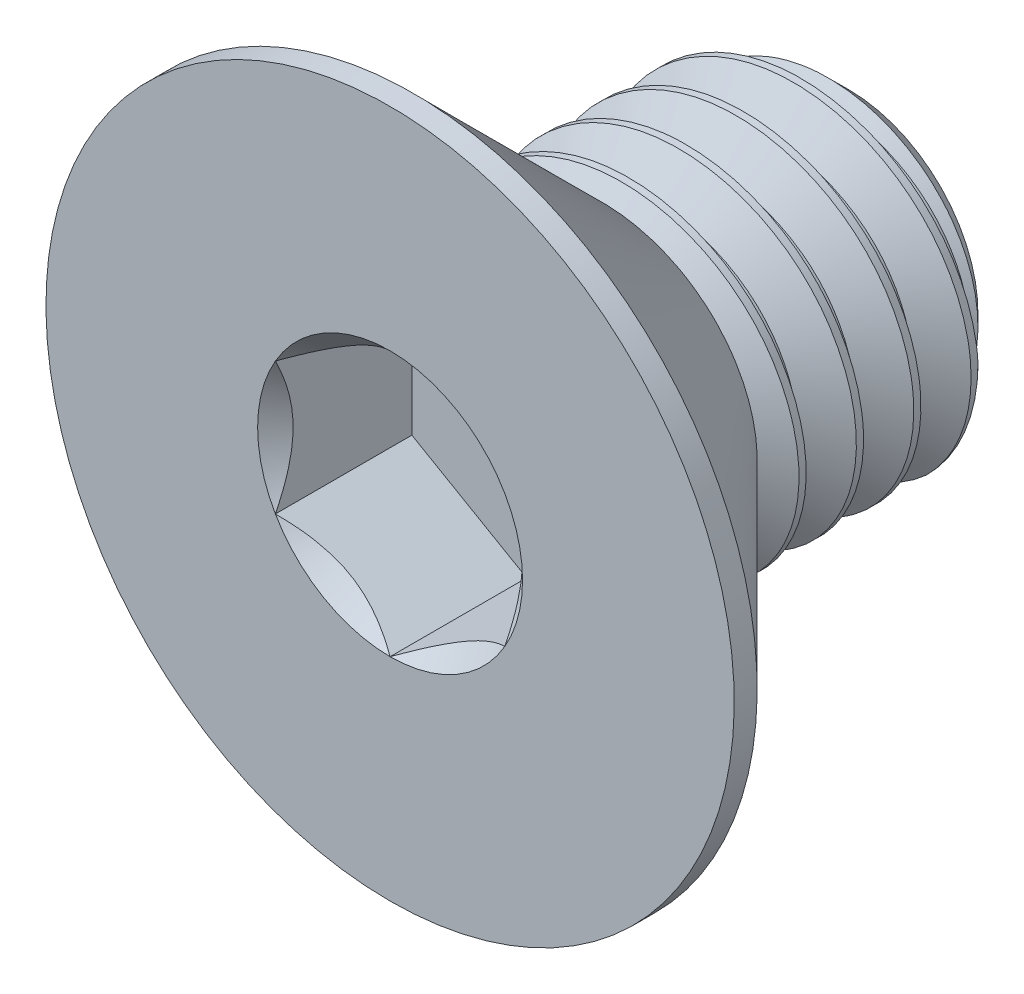
SolidWorks part; units mm, degrees
ref_plane "Front" through (0, 0, 0) normal (0, 0, 1) x (1, 0, 0)
ref_plane "Top" through (0, 0, 0) normal (0, 1, 0) x (1, 0, 0)
ref_plane "Right" through (0, 0, 0) normal (1, 0, 0) x (0, 0, -1)
sketch "Sketch1" plane through (0, 0, 0) normal (1, 0, 0) x (0, 0, -1)
  line L0 (0, 3) -> (0.2, 3) construction
  line L1 (0.2, 3) -> (1.7, 1.5) construction
  line L2 (0, 1.5) -> (4, 1.5)
  line L3 (4, 1.5) -> (4, 0)
  line L4 (4, 0) -> (0, 0)
  line L5 (0, 0) -> (0, 3) construction
  line L6 (0, 3) -> (0, -3) construction
  line L7 (4, 1.5) -> (4, -1.5) construction
  line L8 (0, -3) -> (0.2, -3) construction
  line L9 (0.2, -3) -> (1.7, -1.5) construction
  line L11 (0, 1.5) -> (0, 0)
  line L12 (1.7, 1.5) -> (1.7, 0) construction
revolve "Revolve1" add sketch "Sketch1" angle 360 mid plane about L4
sketch "Sketch3" plane through (0, 0, -4) normal (0, 0, -1) x (-1, 0, 0)
  circle A0 centre (0, 0) radius 1.5
curve "Helix/Spiral1" pitch 0.5 height 4 radius 1.5 centre (0, 0, -4) axis (0, 0, 1) start towards (0, 1, 0)
sketch "Sketch2" plane through (0, 0, 0) normal (1, 0, 0) x (0, 0, -1)
  line L0 (4, 1.5) -> (4.4375, 1.5)
  line L1 (4.4375, 1.5) -> (4.25, 1.1752)
  line L2 (4.25, 1.1752) -> (4.1875, 1.1752)
  line L3 (4.1875, 1.1752) -> (4, 1.5)
  line L4 (4.0938, 1.3376) -> (4.3437, 1.3376) construction
  dimension "D1" = 60
  dimension "D2" = 0.0625
  dimension "D3" = 0.25
chamfer "Chamfer1" distance 0.375 angle 45 1 edges at (0, 1.5, -4)
sweep "Cut-Sweep1" cut profiles "Sketch2" path "Helix/Spiral1" align with end faces yes
sketch "Sketch7" plane through (0, 0, 0) normal (1, 0, 0) x (0, 0, -1)
  line L0 (0, 3) -> (0.2, 3) construction
  line L1 (0.2, 3) -> (1.7, 1.5) construction
  line L2 (0, 3) -> (0.2, 3)
  line L3 (0.2, 3) -> (1.7, 1.5)
  line L4 (1.7, 1.5) -> (1.7, 0) construction
  line L5 (1.7, 1.5) -> (1.7, 0)
  line L7 (0, 0) -> (0, 3) construction
  line L8 (0, 0) -> (0, 3)
  line L9 (0, 0) -> (1.7, 0)
  line L10 (3.3, 0) -> (-3.3, 0) construction
revolve "Revolve2" add sketch "Sketch7" angle 360 mid plane about L9
ref_plane "Plane1" through (0, 0, -1.7) normal (0, 0, 1) x (1, 0, 0)
sketch "Sketch8" plane through (0, 0, -1.7) normal (0, 0, 1) x (1, 0, 0)
  circle A0 centre (0, 0) radius 1.5
extrude "Boss-Extrude1" add sketch "Sketch8" against normal through all draft 45
sketch "Sketch5" plane through (0, 0, 0) normal (0, 0, 1) x (1, 0, 0)
  line L1 (1, -0.5774) -> (1, 0.5774)
  line L2 (1, 0.5774) -> (0, 1.1547)
  line L3 (0, 1.1547) -> (-1, 0.5774)
  line L4 (-1, 0.5774) -> (-1, -0.5774)
  line L5 (-1, -0.5774) -> (0, -1.1547)
  line L6 (0, -1.1547) -> (1, -0.5774)
  circle A0 centre (0, 0) radius 1 construction
  dimension "Hex" = 2
extrude "Cut-Extrude2" cut sketch "Sketch5" against normal blind 1.19
sketch "Sketch6" plane through (0, 0, 0) normal (0, 0, 1) x (1, 0, 0)
  circle A0 centre (0, 0) radius 1.1547
extrude "Cut-Extrude3" cut sketch "Sketch6" against normal blind 1.19 draft 45
sketch "Sketch9" [suppressed] plane through (0, 0, -5.5) normal (0, 0, 1) x (1, 0, 0)
  circle A1 centre (0, 0) radius 5
  circle A2 centre (0, 0) radius 5
  point P0 (0, 5)
  dimension "D1" = 0
extrude "Boss-Extrude2" [suppressed] add sketch "Sketch9" against normal offset from surface (18.5 mm away) 26 up to face at (0, 1.125, -4)
fillet "Fillet1" [suppressed] radius 0.3
sketch "Sketch10" plane through (0, 0, 0) normal (1, 0, 0) x (0, 0, -1)
  line L0 (4, 1.5) -> (4, -1.5) construction
  point P0 (3.25, -1.5)
  dimension "D1" = 0.75
equation "\"D3@Helix/Spiral1\" = \"Lg@Sketch1\""
equation "\"D2@Sketch2\" = \"D4@Helix/Spiral1\" * .125"
equation "\"D3@Sketch2\" = \"D4@Helix/Spiral1\" * .5"
equation "\"D1@Chamfer1\" = \"D4@Helix/Spiral1\" * .75"
equation "\"D1@Cut-Extrude2\" = \"Head Ht@Sketch1\" * .7"
equation "\"D1@Sketch10\" = \"D4@Helix/Spiral1\" * 1.5"
equation "\"D1@Cut-Extrude3\" = \"D1@Cut-Extrude2\""
equation "\"D1@Fillet1\" = \"Dia@Sketch1\" * .1"
